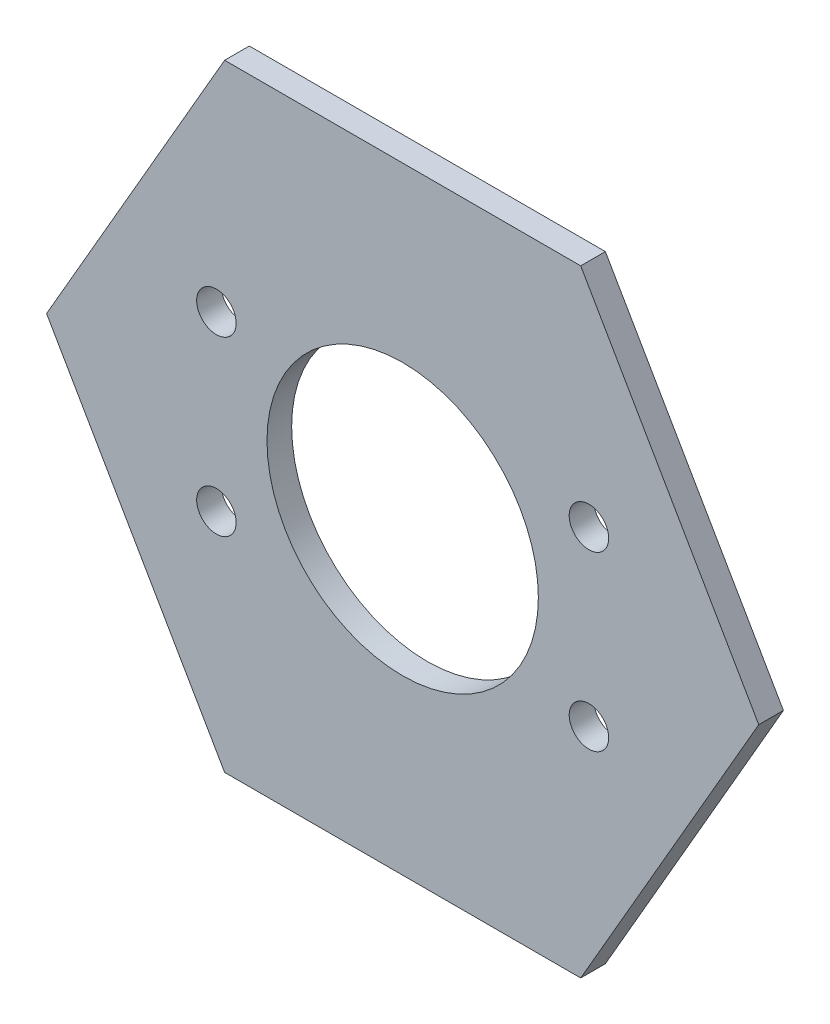
SolidWorks part; units mm, degrees
ref_plane "Front Plane" through (0, 0, 0) normal (0, 0, 1) x (1, 0, 0)
ref_plane "Top Plane" through (0, 0, 0) normal (0, 1, 0) x (1, 0, 0)
ref_plane "Right Plane" through (0, 0, 0) normal (1, 0, 0) x (0, 0, -1)
sketch "Sketch1" plane through (0, 0, 0) normal (0, 0, 1) x (1, 0, 0)
  line L0 (0, 0) -> (0, -25) construction
  line L1 (-8.5, -17.5) -> (8.5, -17.5) construction
  line L2 (-14.4338, 25) -> (14.4338, 25)
  line L3 (-5, -19) -> (5, -19) construction
  line L4 (-5, -19) -> (-5, -24) construction
  line L5 (-5, -24) -> (5, -24) construction
  line L6 (5, -19) -> (5, -24) construction
  line L7 (14.4338, 25) -> (28.8675, 0)
  line L8 (28.8675, 0) -> (14.4338, -25)
  line L9 (14.4338, -25) -> (-14.4338, -25)
  line L10 (-14.4338, -25) -> (-28.8675, 0)
  line L11 (-28.8675, 0) -> (-14.4338, 25)
  circle A0 centre (0, 0) radius 8 construction
  circle A1 centre (0, 0) radius 11
  circle A2 centre (-15.1, -7) radius 1.6 construction
  circle A3 centre (-15.1, 7) radius 1.6 construction
  circle A4 centre (15.1, 7) radius 1.6 construction
  circle A5 centre (15.1, -7) radius 1.6 construction
  circle A6 centre (-15.1, -7) radius 1.6
  circle A7 centre (-15.1, 7) radius 1.6
  circle A8 centre (15.1, 7) radius 1.6
  circle A9 centre (15.1, -7) radius 1.6
  circle A10 centre (0, 0) radius 25 construction
  dimension "D2" = 50
  dimension "D3" = 5
  dimension "D4" = 10
  dimension "D5" = 1
  dimension "D1" = 3
extrude "Boss-Extrude1" add sketch "Sketch1" along normal blind 2
